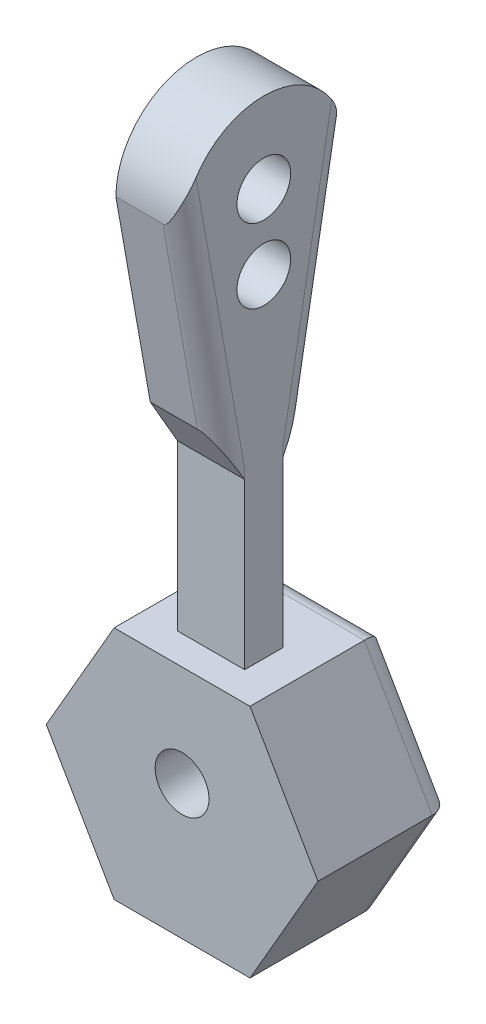
SolidWorks part; units mm, degrees
ref_plane "Ön Düzlem" through (0, 0, 0) normal (0, 0, 1) x (1, 0, 0)
ref_plane "Üst Düzlem" through (0, 0, 0) normal (0, 1, 0) x (1, 0, 0)
ref_plane "Sağ Düzlem" through (0, 0, 0) normal (1, 0, 0) x (0, 0, -1)
sketch "Sketch1" plane through (0, 0, 0) normal (0, 0, 1) x (1, 0, 0)
  line L0 (-20.2073, 0) -> (20.2073, 0) construction
  line L1 (-10.1036, -17.5) -> (10.1036, -17.5)
  line L2 (10.1036, -17.5) -> (20.2073, 0)
  line L3 (20.2073, 0) -> (10.1036, 17.5)
  line L4 (10.1036, 17.5) -> (-10.1036, 17.5)
  line L5 (-10.1036, 17.5) -> (-20.2073, 0)
  line L6 (-20.2073, 0) -> (-10.1036, -17.5)
  circle A0 centre (0, 0) radius 17.5 construction
  circle A1 centre (0, 2.5) radius 4
  point P1 (0, 2.5)
  point P10 (0, 0)
  dimension "D3" = 8
  dimension "D1" = 35
  dimension "D2" = 2.5
extrude "Boss-Extrude1" add sketch "Sketch1" against normal blind 20
fillet "Fillet1" radius 3 6 edges at (-15.1554, 8.75, -20) (-15.1554, -8.75, -20) (0, -17.5, -20) (15.1554, -8.75, -20) (15.1554, 8.75, -20) (0, 17.5, -20)
sketch "Sketch3" plane through (0, 0, 0) normal (1, 0, 0) x (0, 0, -1)
  line L0 (17, 0) -> (17, 17.5) construction
  line L1 (10, 42) -> (14.0415, 49)
  line L2 (17, 17.5) -> (0, 17.5) construction
  line L3 (14.0415, 49) -> (19.1549, 78)
  line L4 (17.252, 84.4845) -> (9.7609, 42)
  line L5 (7.1549, 78) -> (7.1549, 17.5) construction
  line L6 (4.3099, 42) -> (0.2684, 49)
  line L7 (0.2684, 49) -> (-4.8451, 78)
  line L8 (-2.9422, 84.4845) -> (4.549, 42)
  line L9 (4.549, 42) -> (4.3099, 42)
  line L10 (9.7609, 42) -> (10, 42)
  line L11 (10, 42) -> (10, 17.5)
  line L12 (9.7609, 42) -> (9.7609, 17.5)
  line L13 (4.549, 42) -> (4.549, 17.5)
  line L14 (4.3099, 42) -> (4.3099, 17.5)
  line L15 (4.549, 42) -> (9.7609, 42)
  line L16 (4.3099, 17.5) -> (10, 17.5)
  circle A0 centre (7.1549, 78) radius 4
  arc A1 (19.1549, 78) -> (-4.8451, 78) centre (7.1549, 78) ccw
  circle A2 centre (7.1549, 66.99) radius 4
  dimension "D8" = 8
  dimension "D1" = 7
  dimension "D2" = 60
  dimension "D3" = 7
  dimension "D4" = 29
  dimension "D5" = 80
  dimension "D6" = 3
  dimension "D7" = 60.5
  dimension "D9" = 12
  dimension "D10" = 11.01
extrude "Boss-Extrude2" add sketch "Sketch3" along normal mid plane 10
fillet "Fillet4" radius 3 2 edges at (5, 63.5, -16.5982) (5, 63.5, 2.2883)
fillet "Fillet6" radius 3 1 edges at (4, 2.5, -20)
